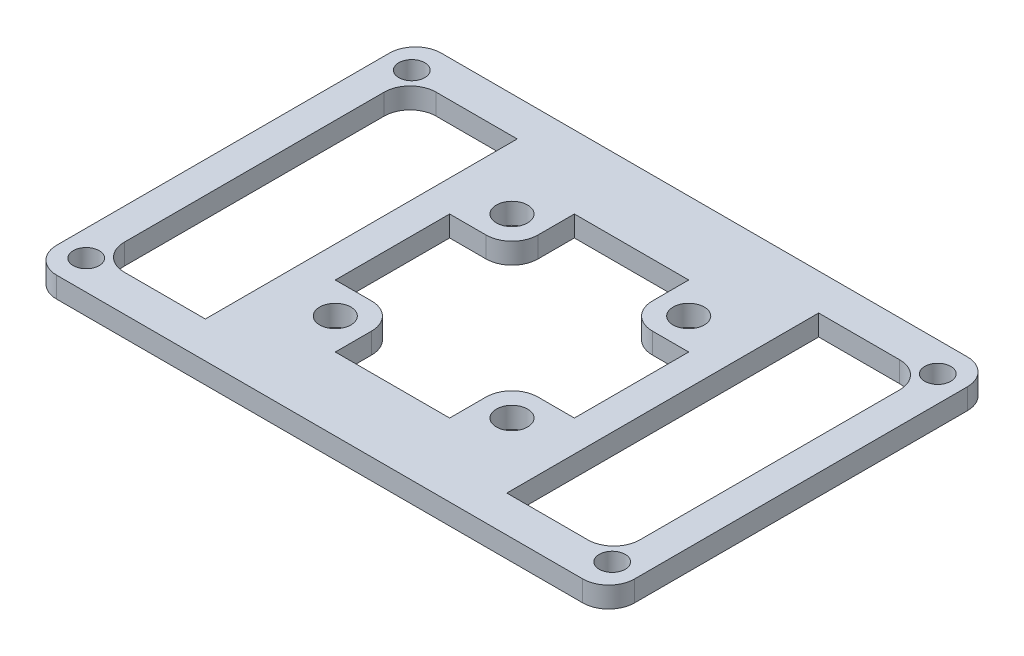
SolidWorks part; units mm, degrees
ref_plane "Front Plane" through (0, 0, 0) normal (0, 0, 1) x (1, 0, 0)
ref_plane "Top Plane" through (0, 0, 0) normal (0, 1, 0) x (1, 0, 0)
ref_plane "Right Plane" through (0, 0, 0) normal (1, 0, 0) x (0, 0, -1)
sketch "Sketch1" plane through (0, 0, 0) normal (0, 1, 0) x (1, 0, 0)
  line L1 (-27.8, 18.5) -> (27.8, 18.5)
  line L2 (-27.8, 18.5) -> (-27.8, -18.5)
  line L3 (-27.8, -18.5) -> (27.8, -18.5)
  line L4 (27.8, 18.5) -> (27.8, -18.5)
  line L5 (-27.8, 18.5) -> (27.8, -18.5) construction
  line L6 (-27.8, -18.5) -> (27.8, 18.5) construction
  point P0 (0, 0)
  dimension "D1" = 37
  dimension "D2" = 55.6
extrude "Boss-Extrude1" add sketch "Sketch1" along normal blind 2
sketch "Sketch3" plane through (0, 2, 0) normal (0, 1, 0) x (1, 0, 0)
  line L0 (0, 8.5) -> (0, -8.5) construction
  line L1 (-8.5, 8.5) -> (8.5, 8.5)
  line L2 (-8.5, 8.5) -> (-8.5, -8.5)
  line L3 (-8.5, -8.5) -> (8.5, -8.5)
  line L4 (8.5, 8.5) -> (8.5, -8.5)
  line L5 (-8.5, 8.5) -> (8.5, -8.5) construction
  line L6 (-8.5, -8.5) -> (8.5, 8.5) construction
  line L7 (-8.5, 0) -> (8.5, 0) construction
  circle A0 centre (-8.5, 8.5) radius 1.5
  circle A1 centre (-8.5, 8.5) radius 2.5
  circle A2 centre (-8.5, -8.5) radius 2.5
  circle A3 centre (-8.5, -8.5) radius 1.5
  circle A4 centre (8.5, -8.5) radius 1.5
  circle A5 centre (8.5, -8.5) radius 2.5
  circle A6 centre (8.5, 8.5) radius 2.5
  circle A7 centre (8.5, 8.5) radius 1.5
  point P0 (0, 0)
  dimension "D3" = 3
  dimension "D4" = 5
  dimension "D1" = 17
  dimension "D2" = 17
sketch "Sketch5" plane through (0, 2, 0) normal (0, 1, 0) x (1, 0, 0)
  line L0 (0, 11.5) -> (0, -11.5) construction
  line L5 (-11.5, 11.5) -> (11.5, 11.5)
  line L6 (-11.5, 11.5) -> (-11.5, -11.5)
  line L15 (-11.5, -11.5) -> (11.5, -11.5)
  line L16 (11.5, 11.5) -> (11.5, -11.5)
  line L21 (-11.5, 11.5) -> (11.5, -11.5) construction
  line L22 (-11.5, -11.5) -> (11.5, 11.5) construction
  line L23 (-11.5, 11.5) -> (-5.5, 11.5)
  line L24 (-11.5, 11.5) -> (-11.5, 5.5)
  line L25 (-11.5, 5.5) -> (-8, 5.5)
  line L26 (-5.5, 11.5) -> (-5.5, 8)
  line L27 (-11.5, 0) -> (11.5, 0) construction
  line L28 (11.5, 5.5) -> (8, 5.5)
  line L29 (5.5, 11.5) -> (5.5, 8)
  line L30 (11.5, 11.5) -> (5.5, 11.5)
  line L31 (11.5, 11.5) -> (11.5, 5.5)
  line L32 (11.5, -11.5) -> (5.5, -11.5)
  line L33 (5.5, -11.5) -> (5.5, -8)
  line L34 (11.5, -5.5) -> (8, -5.5)
  line L35 (11.5, -11.5) -> (11.5, -5.5)
  line L36 (-11.5, -5.5) -> (-8, -5.5)
  line L37 (-5.5, -11.5) -> (-5.5, -8)
  line L38 (-11.5, -11.5) -> (-5.5, -11.5)
  line L39 (-11.5, -11.5) -> (-11.5, -5.5)
  arc A0 (5.5, -8) -> (8, -5.5) centre (8, -8) cw
  arc A1 (-8, -5.5) -> (-5.5, -8) centre (-8, -8) cw
  arc A2 (8, 5.5) -> (5.5, 8) centre (8, 8) cw
  arc A3 (-8, 5.5) -> (-5.5, 8) centre (-8, 8) ccw
  point P0 (0, 0)
  point P25 (5.5, -5.5)
  point P28 (-5.5, -5.5)
  point P31 (5.5, 5.5)
  point P34 (-5.5, 5.5)
  dimension "D4" = 2.5
  dimension "D1" = 23
  dimension "D2" = 23
  dimension "D3" = 6
extrude "Cut-Extrude2" cut sketch "Sketch5" against normal up to next contours L5 L15 region at (0, 2, 0)
fillet "Fillet2" radius 2.5 4 edges at (27.8, 1, -18.5) (-27.8, 1, -18.5) (27.8, 1, 18.5) (-27.8, 1, 18.5)
sketch "Sketch6" plane through (0, 2, 0) normal (0, 1, 0) x (1, 0, 0)
  line L0 (-27.8, 0) -> (-11.5, 0) construction
  line L1 (-27.8, 16) -> (-27.8, -16) construction
  line L2 (-11.5, 5.5) -> (-11.5, -5.5) construction
  line L3 (25.3, 18.5) -> (-25.3, 18.5) construction
  line L4 (-22.3, 15) -> (-14.5, 15)
  line L5 (-24.8, 12.5) -> (-24.8, -12.5)
  line L6 (-22.3, -15) -> (-14.5, -15)
  line L7 (-14.5, 15) -> (-14.5, -15)
  line L8 (-24.8, 15) -> (-14.5, -15) construction
  line L9 (-24.8, -15) -> (-14.5, 15) construction
  line L10 (0, 18.5) -> (0, -18.5) construction
  line L11 (-25.3, -18.5) -> (25.3, -18.5) construction
  line L12 (22.3, -15) -> (14.5, -15)
  line L13 (14.5, 15) -> (14.5, -15)
  line L14 (22.3, 15) -> (14.5, 15)
  line L15 (24.8, 12.5) -> (24.8, -12.5)
  arc A0 (-24.8, -12.5) -> (-22.3, -15) centre (-22.3, -12.5) ccw
  arc A1 (-22.3, 15) -> (-24.8, 12.5) centre (-22.3, 12.5) ccw
  arc A2 (24.8, -12.5) -> (22.3, -15) centre (22.3, -12.5) cw
  arc A3 (22.3, 15) -> (24.8, 12.5) centre (22.3, 12.5) cw
  point P6 (-19.65, 0)
  point P11 (-18.4, 15)
  point P14 (-24.8, 0)
  dimension "D3" = 2.5
  dimension "D1" = 3.5
  dimension "D2" = 3
extrude "Cut-Extrude3" cut sketch "Sketch6" against normal up to next
sketch "Sketch7" plane through (0, 2, 0) normal (0, 1, 0) x (1, 0, 0)
  line L0 (25.3, 18.5) -> (-25.3, 18.5) construction
  line L1 (-27.8, 16) -> (-27.8, -16) construction
  line L2 (0, 18.5) -> (0, -18.5) construction
  line L3 (-25.3, -18.5) -> (25.3, -18.5) construction
  line L4 (-27.8, 0) -> (27.8, 0) construction
  line L5 (27.8, -16) -> (27.8, 16) construction
  circle A0 centre (-25.3, 15.66) radius 1.25
  circle A1 centre (25.3, 15.66) radius 1.25
  circle A2 centre (25.3, -15.66) radius 1.25
  circle A3 centre (-25.3, -15.66) radius 1.25
  dimension "D3" = 2.5
  dimension "D1" = 2.84
  dimension "D2" = 2.5
extrude "Cut-Extrude4" cut sketch "Sketch7" against normal up to next
extrude "Cut-Extrude5" cut sketch "Sketch3" against normal blind 10 contours L1 A0 L2 | A7 L1 L4 | A7 L4 L1 | L2 A0 L1 | A3 L2 L3 | A3 L3 L2 | L4 A4 L3 | L3 A4 L4 region at (-8.7122, 2, -8.7122) region at (-7.8634, 2, -7.8634) region at (8.7122, 2, -8.7122) region at (7.8634, 2, -7.8634) region at (-7.8634, 2, 7.8634) region at (-8.7122, 2, 8.7122) region at (8.7122, 2, 8.7122) region at (7.8634, 2, 7.8634)
